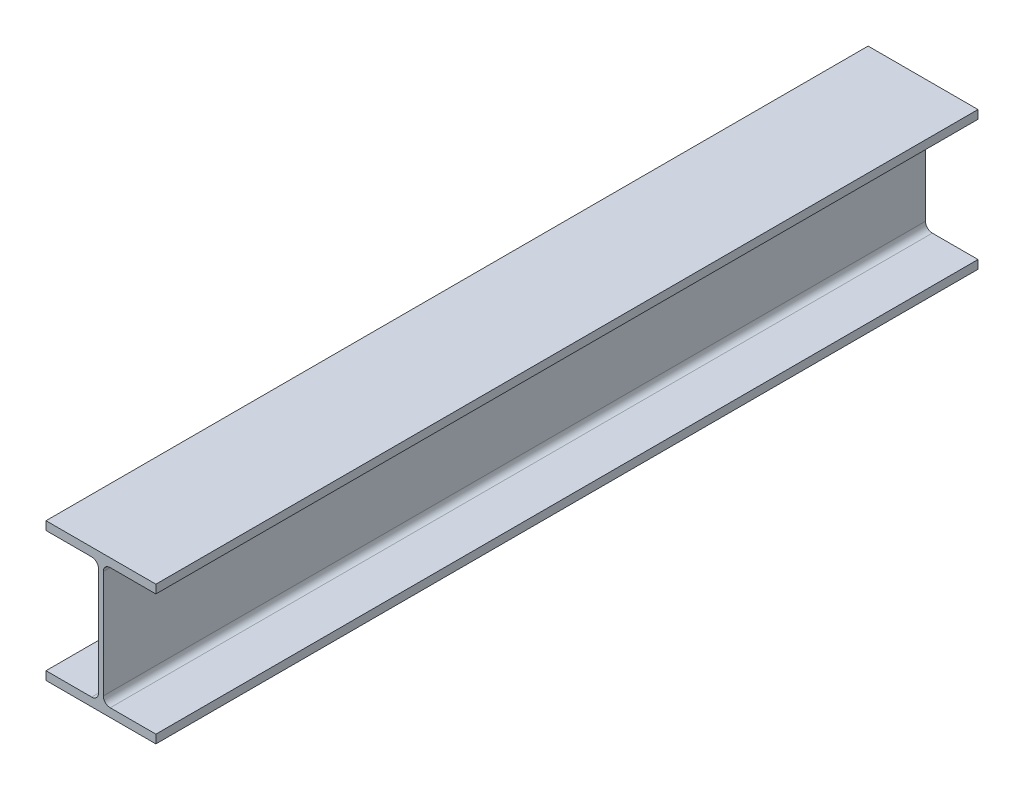
SolidWorks part; units mm, degrees
ref_plane "Plane1" through (0, 0, 0) normal (0, 0, 1) x (1, 0, 0)
ref_plane "Plane2" through (0, 0, 0) normal (0, 1, 0) x (1, 0, 0)
ref_plane "Plane3" through (0, 0, 0) normal (1, 0, 0) x (0, 0, -1)
sketch "Sketch1" plane through (0, 0, 0) normal (0, 0, 1) x (1, 0, 0)
  line L0 (0, 0) -> (0, 15.748)
  line L1 (0, 15.748) -> (84.709, 15.748)
  line L2 (97.409, 28.448) -> (97.409, 228.092)
  line L3 (84.709, 240.792) -> (0, 240.792)
  line L4 (0, 240.792) -> (0, 256.54)
  line L5 (0, 256.54) -> (203.708, 256.54)
  line L6 (203.708, 256.54) -> (203.708, 240.792)
  line L7 (203.708, 240.792) -> (118.999, 240.792)
  line L8 (106.299, 228.092) -> (106.299, 28.448)
  line L9 (118.999, 15.748) -> (203.708, 15.748)
  line L10 (203.708, 15.748) -> (203.708, 0)
  line L11 (203.708, 0) -> (0, 0)
  line L12 (101.854, -72.1361) -> (101.854, 256.54) construction
  arc A0 (84.709, 15.748) -> (97.409, 28.448) centre (84.709, 28.448) ccw
  arc A1 (97.409, 228.092) -> (84.709, 240.792) centre (84.709, 228.092) ccw
  arc A2 (118.999, 240.792) -> (106.299, 228.092) centre (118.999, 228.092) ccw
  arc A3 (106.299, 28.448) -> (118.999, 15.748) centre (118.999, 28.448) ccw
  dimension "D2" = 15.748
  dimension "D1" = 4.445
extrude "BaseSteelW" add sketch "Sketch1" against normal mid plane 1524
equation "\"D1@Sketch1\" = \"Tw@Sketch1\" / 2"
equation "\"D2@Sketch1\" = \"Tf@Sketch1\""
